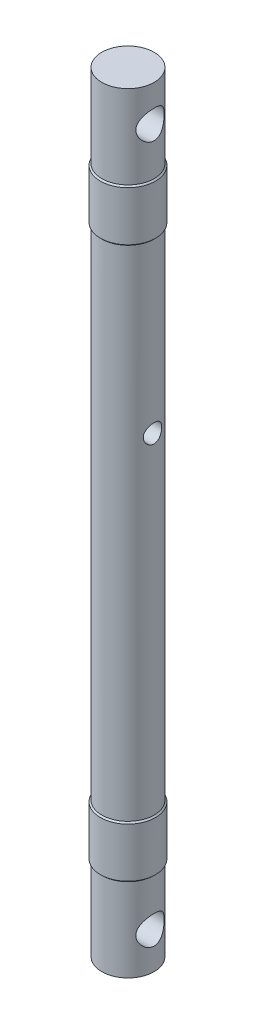
SolidWorks part; units mm, degrees
material "ABS"
ref_plane "Front Plane" through (0, 0, 0) normal (0, 0, 1) x (1, 0, 0)
ref_plane "Top Plane" through (0, 0, 0) normal (0, 1, 0) x (1, 0, 0)
ref_plane "Right Plane" through (0, 0, 0) normal (1, 0, 0) x (0, 0, -1)
sketch "Sketch1" plane through (0, 0, 0) normal (0, 1, 0) x (1, 0, 0)
  circle A0 centre (0, 0) radius 3.7
  dimension "D1" = 7.4
extrude "Boss-Extrude1" add sketch "Sketch1" along normal blind 109
hole_wizard "Ø4.0mm Dowel Hole1" positions "Sketch3" profile "Sketch4" hole size "Ø4.0" standard "ANSI Metric" end condition up to next
sketch "Sketch3" plane through (0, 0, 0) normal (1, 0, 0) x (0, 0, -1)
  line L0 (3.7, 109) -> (-3.7, 109) construction
  line L1 (-3.7, 0) -> (3.7, 0) construction
  point P0 (0, 5.15)
  point P2 (0, 103.85)
  dimension "D1" = 5.15
  dimension "D2" = 5.15
sketch "Sketch4" plane through (0, 5.15, 0) normal (0, 1, 0) x (0, 0, -1)
  line L0 (0, 0) -> (0, 3.7)
  line L1 (0, 3.7) -> (2, 3.7)
  line L2 (2, 3.7) -> (2, 0.025)
  line L3 (2, 0.025) -> (2.025, 0)
  line L5 (2.025, 0) -> (0, 0)
  line L6 (-2, 0.025) -> (-2.025, 0) construction
  line L11 (0, -6.35) -> (0, 107.95) construction
  dimension "Thru Hole Dia." = 4
  dimension "Thru Hole Depth" = 3.7
  dimension "Near C'Sink Dia." = 4.05
  dimension "Near C'Sink Angle" = 90
hole_wizard "Ø4.0mm Dowel Hole2" positions "Sketch5" profile "Sketch6" hole size "Ø4.0" standard "ANSI Metric" end condition through all
sketch "Sketch5" plane through (0, 0, 0) normal (1, 0, 0) x (0, 0, -1)
  line L0 (3.7, 109) -> (-3.7, 109) construction
  line L1 (-3.7, 0) -> (3.7, 0) construction
  point P0 (0, 103.85)
  point P2 (0, 5.15)
  dimension "D1" = 5.15
  dimension "D2" = 5.15
sketch "Sketch6" plane through (0, 103.85, 0) normal (0, 1, 0) x (0, 0, 1)
  line L0 (0, 0) -> (0, 3.7)
  line L1 (0, 3.7) -> (2, 3.7)
  line L2 (2, 3.7) -> (2, 0.025)
  line L3 (2, 0.025) -> (2.025, 0)
  line L5 (2.025, 0) -> (0, 0)
  line L6 (-2, 0.025) -> (-2.025, 0) construction
  line L11 (0, -6.35) -> (0, 107.95) construction
  dimension "Thru Hole Dia." = 4
  dimension "Thru Hole Depth" = 3.7
  dimension "Near C'Sink Dia." = 4.05
  dimension "Near C'Sink Angle" = 90
sketch "Sketch7" plane through (0, 0, 0) normal (1, 0, 0) x (0, 0, -1)
  line L0 (3.7, 0) -> (3.7, 109) construction
  line L1 (3.7, 109) -> (-3.7, 109) construction
  line L2 (3.7, 97) -> (3.9, 97)
  line L3 (3.7, 97) -> (3.7, 90)
  line L4 (3.7, 90) -> (3.9, 90)
  line L5 (3.9, 97) -> (3.9, 90)
  line L6 (0, 99.2222) -> (0, 85.4987) construction
  line L7 (-3.7, 0) -> (3.7, 0) construction
  line L8 (3.7, 19) -> (3.9, 19)
  line L9 (3.7, 19) -> (3.7, 12)
  line L10 (3.7, 12) -> (3.9, 12)
  line L11 (3.9, 19) -> (3.9, 12)
  dimension "D1" = 12
  dimension "D2" = 7
  dimension "D3" = 0.2
  dimension "D4" = 12
  dimension "D5" = 7
  dimension "D6" = 0.2
revolve "Revolve1" add sketch "Sketch7" angle 360 about L6
chamfer "Chamfer1" distance 0.2 angle 45 4 edges at (0, 90, 3.7) (0, 97, -3.7) (0, 19, -3.7) (0, 12, 3.7)
sketch "Sketch8" plane through (0, 0, 0) normal (1, 0, 0) x (0, 0, -1)
  line L1 (3.7, 109) -> (-3.7, 109) construction
  circle A0 centre (0, 66) radius 1.3
  dimension "D1" = 2.6
  dimension "D2" = 43
extrude "Cut-Extrude2" cut sketch "Sketch8" against normal through all both and the other way through all
